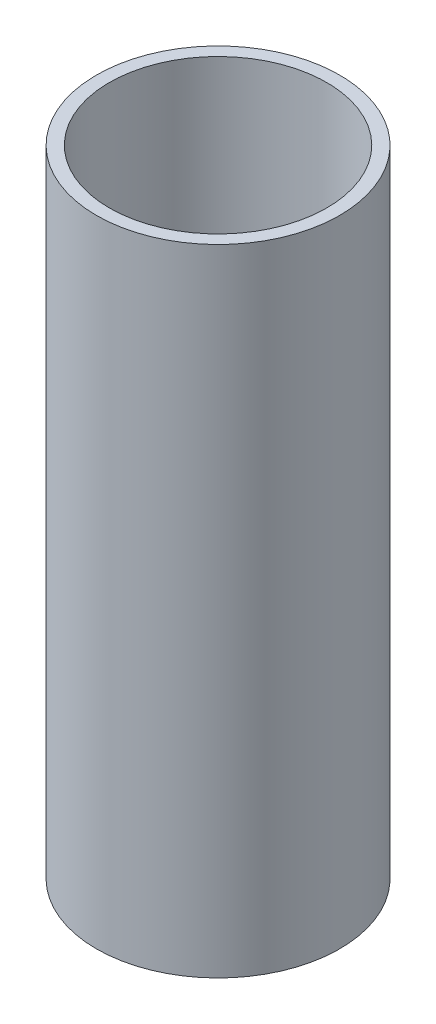
SolidWorks part; units mm, degrees
ref_plane "Front Plane" through (0, 0, 0) normal (0, 0, 1) x (1, 0, 0)
ref_plane "Top Plane" through (0, 0, 0) normal (0, 1, 0) x (1, 0, 0)
ref_plane "Right Plane" through (0, 0, 0) normal (1, 0, 0) x (0, 0, -1)
sketch "Sketch1" plane through (0, 0, 0) normal (0, 1, 0) x (1, 0, 0)
  circle A0 centre (0, 0) radius 40
  dimension "SLEEVE_OD" = 80
extrude "Boss-Extrude1" add sketch "Sketch1" along normal blind 208.9263
sketch "Sketch2" plane through (0, 0, 0) normal (0, 1, 0) x (1, 0, 0)
  circle A0 centre (0, 0) radius 35.7524
  dimension "BORE_D" = 71.5048
extrude "Cut-Extrude1" cut sketch "Sketch2" along normal through all
chamfer "Chamfer1" distance 2.2396 angle 60 rebuild error yes
